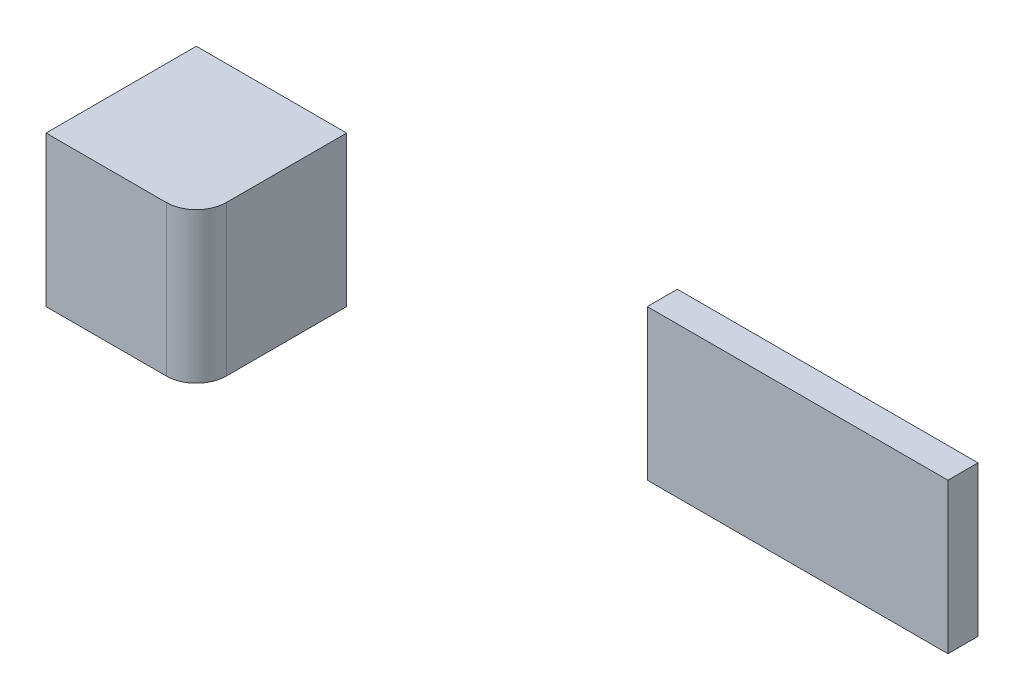
SolidWorks part; units mm, degrees
ref_plane "前视基准面" through (0, 0, 0) normal (0, 0, 1) x (1, 0, 0)
ref_plane "上视基准面" through (0, 0, 0) normal (0, 1, 0) x (1, 0, 0)
ref_plane "右视基准面" through (0, 0, 0) normal (1, 0, 0) x (0, 0, -1)
other "Configuration Table"
sketch "草图1" plane through (0, 0, 0) normal (0, 0, 1) x (1, 0, 0)
  line L1 (0, 0) -> (10, 0)
  line L2 (0, 0) -> (0, 10)
  line L3 (0, 10) -> (10, 10)
  line L4 (10, 0) -> (10, 10)
extrude "凸台-拉伸1" add sketch "草图1" along normal blind 10
fillet "圆角1" radius 2 1 edges at (10, 5, 10) tangent propagation no
sketch "草图2" plane through (0, 0, 0) normal (0, 0, 1) x (1, 0, 0)
  line L1 (30, 0) -> (50, 0)
  line L2 (30, 0) -> (30, 10)
  line L3 (30, 10) -> (50, 10)
  line L4 (50, 0) -> (50, 10)
base flange "基体-法兰1" sketch "草图2" thickness 2 reverse thickness direction no parameters "D1"=3
sketch "折弯-线1" plane through (0, 0, 0) normal (0, 1, 0) x (1, 0, 0)
sketch "边界框1" plane through (0, 0, 0) normal (0, 1, 0) x (1, 0, 0)
sheet metal parameters "钣金7" thickness 2 parameters "D1"=3
flat pattern "平板型式7" [suppressed]
sketch "折弯-线2" plane through (0, 0, 0) normal (0, 1, 0) x (1, 0, 0)
sketch "边界框2" [suppressed] plane through (0, 0, 0) normal (0, 1, 0) x (1, 0, 0)
